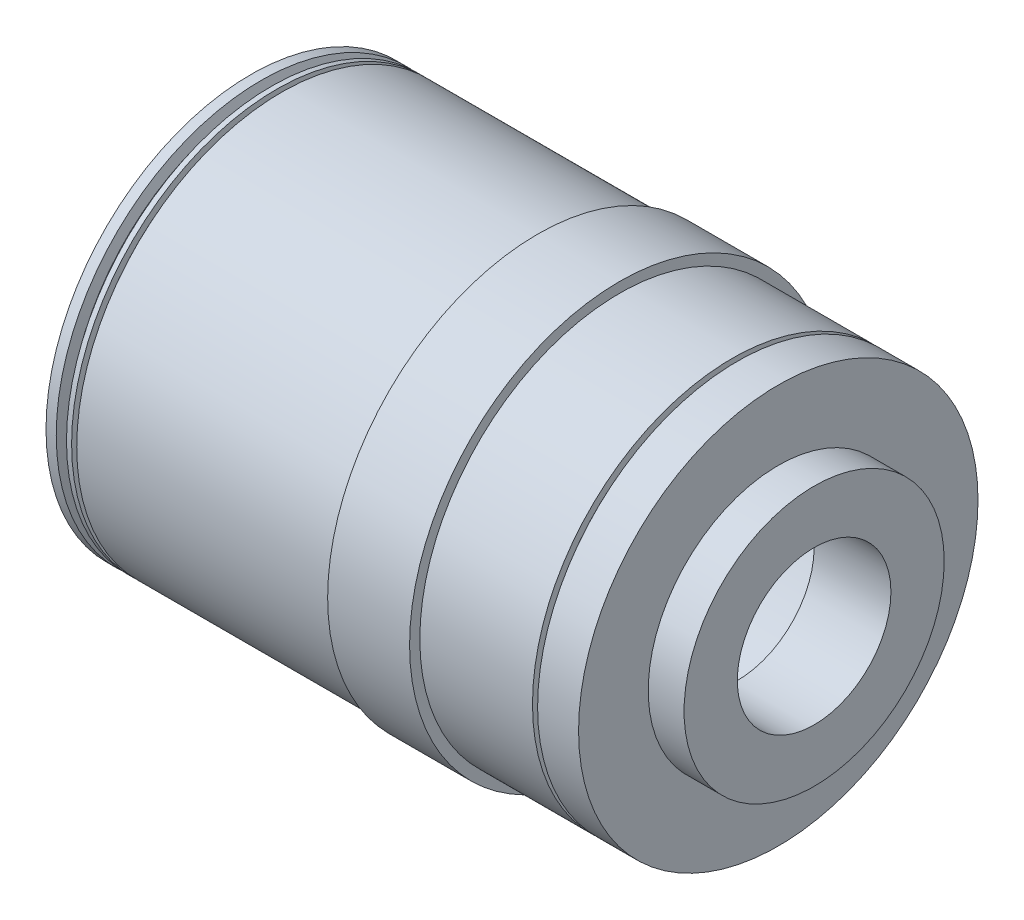
SolidWorks part; units mm, degrees
material "PVC Rigid"
ref_plane "Front" through (0, 0, 0) normal (0, 0, 1) x (1, 0, 0)
ref_plane "Top" through (0, 0, 0) normal (0, 1, 0) x (1, 0, 0)
ref_plane "Right" through (0, 0, 0) normal (1, 0, 0) x (0, 0, -1)
sketch "Sketch1" plane through (0, 0, 0) normal (1, 0, 0) x (0, 0, -1)
  circle A0 centre (0, 0) radius 19.5
  circle A1 centre (0, 0) radius 7.5
  dimension "D1" = 39
  dimension "D2" = 15
extrude "Boss-Extrude1" add sketch "Sketch1" along normal blind 4
sketch "Sketch2" plane through (0, 0, 0) normal (-1, 0, 0) x (0, 0, 1)
  circle A0 centre (0, 0) radius 19.5
  circle A1 centre (0, 0) radius 17
  dimension "D1" = 34
extrude "Boss-Extrude2" add sketch "Sketch2" along normal blind 11.5
sketch "Sketch3" plane through (0, 0, 0) normal (0, 0, 1) x (1, 0, 0)
  line L0 (4, 19.5) -> (0, 19.5)
  line L1 (4, 19.5) -> (-11.5, 19.5) construction
  line L2 (0, 19.5) -> (-0.5, 19.5)
  line L3 (-0.5, 19.5) -> (-0.5, 18.8)
  line L4 (-0.5, 18.8) -> (0, 18.8)
  line L5 (0, 18.8) -> (0, 19.5)
  dimension "D1" = 0.5
  dimension "D2" = 4
  dimension "D3" = 0.7
ref_axis "Axis1" through (-11.5, 0, 0) along (1, 0, 0)
revolve "Cut-Revolve1" cut sketch "Sketch3" angle 360 about axis through (-11.5, 0, 0) along (1, 0, 0)
sketch "Sketch4" plane through (-11.5, 0, 0) normal (-1, 0, 0) x (0, 0, 1)
  circle A0 centre (0, 0) radius 20.5
  circle A1 centre (0, 0) radius 17
  dimension "D1" = 41
extrude "Boss-Extrude3" add sketch "Sketch4" along normal blind 8
sketch "Sketch5" plane through (-19.5, 0, 0) normal (-1, 0, 0) x (0, 0, 1)
  circle A0 centre (0, 0) radius 20
  circle A1 centre (0, 0) radius 17
  circle M2 centre (0, 0) radius 17
  dimension "D1" = 40
extrude "Boss-Extrude4" add sketch "Sketch5" along normal blind 28 contours A0 M2 region at (-19.5, 0, -19.4343)
sketch "Sketch6" plane through (0, 0, 0) normal (0, 0, 1) x (1, 0, 0)
  line L0 (-47.5, 20) -> (-44.5, 20)
  line L1 (-19.5, 20) -> (-47.5, 20) construction
  line L2 (-45, 20) -> (-45, 19.3)
  line L3 (-44.5, 20) -> (-44.5, 19.3)
  line L4 (-44.5, 19.3) -> (-45, 19.3)
  line L6 (-45.85, 19.15) -> (-46.15, 19.15)
  line L8 (-46.5, 20) -> (-46.15, 19.15)
  line L9 (-45.5, 20) -> (-45.85, 19.15)
  point P5 (-45, 20)
  point P6 (-45.5, 20)
  point P7 (-46.5, 20)
  dimension "D1" = 3
  dimension "D2" = 0.5
  dimension "D3" = 0.5
  dimension "D4" = 1
  dimension "D5" = 0.7
revolve "Cut-Revolve2" cut sketch "Sketch6" angle 360 about axis through (-11.5, 0, 0) along (1, 0, 0) region at (-44.75, 19.65, 0) region at (-46, 19.6513, 0)
sketch "Sketch7" plane through (4, 0, 0) normal (1, 0, 0) x (0, 0, -1)
  circle A0 centre (0, 0) radius 12.7
  circle A1 centre (0, 0) radius 7.5
  dimension "D1" = 25.4
extrude "Boss-Extrude5" add sketch "Sketch7" along normal blind 3.5
sketch "Sketch8" plane through (-19.5, 0, 0) normal (-1, 0, 0) x (0, 0, 1)
  circle A0 centre (0, 0) radius 20.5
  circle A1 centre (0, 0) radius 3
  dimension "D1" = 6
extrude "Boss-Extrude6" add sketch "Sketch8" against normal blind 5
ref_axis "Axis2" through (7.5, 0, 0) along (-1, 0, 0)
ref_axis "Axis3" through (-14.5, 0, 0) along (-1, 0, 0)
ref_axis "Axis4" through (-47.5, 0, 0) along (1, 0, 0)
